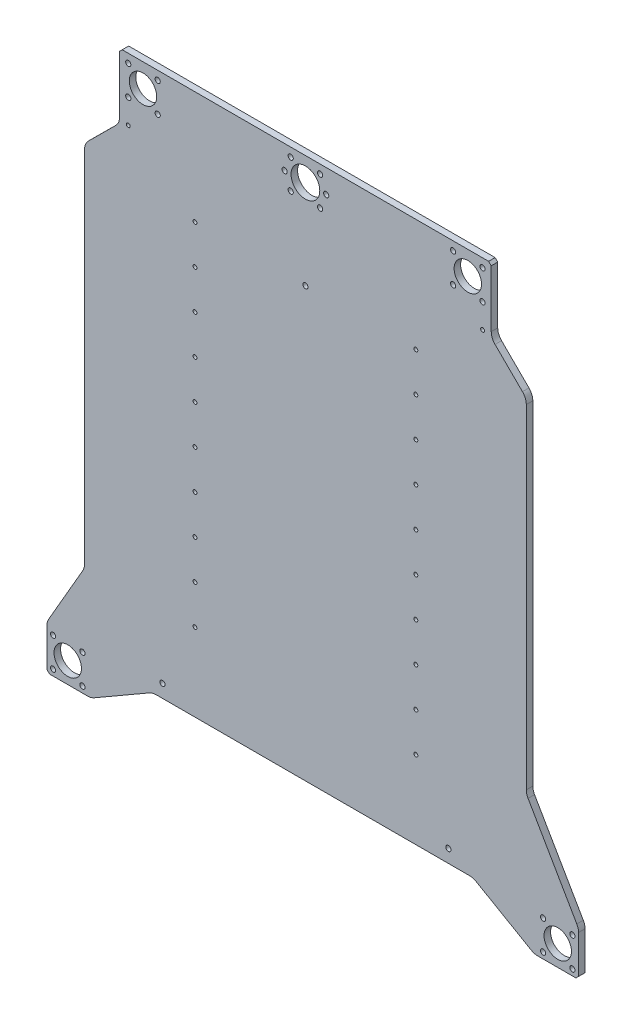
SolidWorks part; units mm, degrees
ref_plane "Front" through (0, 0, 0) normal (0, 0, 1) x (1, 0, 0)
ref_plane "Top" through (0, 0, 0) normal (0, 1, 0) x (1, 0, 0)
ref_plane "Right" through (0, 0, 0) normal (1, 0, 0) x (0, 0, -1)
sketch "Sketch1" plane through (0, 0, 0) normal (0, 0, 1) x (1, 0, 0)
  line L0 (50, 0) -> (-50, 0) construction
  line L1 (-170, -170) -> (0, -170)
  line L2 (-170, -170) -> (-170, 170)
  line L3 (-170, 170) -> (0, 170)
  line L4 (0, -170) -> (0, 170)
  line L5 (-170, -170) -> (0, 170) construction
  line L6 (-170, 170) -> (0, -170) construction
  line L7 (0, -50) -> (0, 50) construction
  point P0 (-85, 0)
  dimension "D1" = 340
  dimension "D2" = 170
extrude "Boss-Extrude1" add sketch "Sketch1" along normal blind 5
sketch "Sketch2" plane through (0, 0, 5) normal (0, 0, 1) x (1, 0, 0)
  line L0 (50, 0) -> (-50, 0) construction
  line L1 (-170, -170) -> (0, -170) construction
  line L2 (-170, -170) -> (-170, 170) construction
  line L3 (-170, 170) -> (0, 170) construction
  line L4 (0, -170) -> (0, 170) construction
  line L5 (-170, -170) -> (0, 170) construction
  line L6 (-170, 170) -> (0, -170) construction
  line L7 (0, -170) -> (0, 170) construction
  line L8 (-170, -170) -> (0, -170) construction
  line L9 (-110, -160) -> (-110, -170) construction
  line L10 (-170, 170) -> (-170, -170) construction
  circle A0 centre (-110, -160) radius 2
  circle A1 centre (0, 160) radius 2
  point P0 (-85, 0)
  dimension "D3" = 4
  dimension "D1" = 170
  dimension "D2" = 340
  dimension "D4" = 60
  dimension "D5" = 10
  dimension "D6" = 10
extrude "Cut-Extrude1" cut sketch "Sketch2" against normal through all
sketch "Sketch3" plane through (0, 0, 5) normal (0, 0, 1) x (1, 0, 0)
  line L0 (-170, 170) -> (-143, 196.8)
  line L1 (-143, 196.8) -> (-143, 246.8)
  line L2 (-143, 246.8) -> (0, 246.8)
  line L3 (0, 246.8) -> (0, 239.85)
  line L4 (0, 217.75) -> (0, 170)
  line L5 (0, 170) -> (-170, 170) construction
  line L6 (-16, 228.8) -> (0, 228.8) construction
  line L7 (0, 228.8) -> (-11.3137, 240.1137) construction
  line L8 (0, 228.8) -> (-11.3137, 217.4863) construction
  line L9 (-125, 228.8) -> (0, 228.8) construction
  line L10 (-21, 213.8) -> (21, 213.8) construction
  line L11 (-21, 213.8) -> (-21, 243.8) construction
  line L12 (-21, 243.8) -> (21, 243.8) construction
  line L13 (21, 213.8) -> (21, 243.8) construction
  line L14 (-21, 213.8) -> (21, 243.8) construction
  line L15 (-21, 243.8) -> (21, 213.8) construction
  line L16 (-141, 212.8) -> (-109, 212.8) construction
  line L17 (-141, 212.8) -> (-141, 244.8) construction
  line L18 (-141, 244.8) -> (-109, 244.8) construction
  line L19 (-109, 212.8) -> (-109, 244.8) construction
  line L20 (-141, 212.8) -> (-109, 244.8) construction
  line L21 (-141, 244.8) -> (-109, 212.8) construction
  line L22 (-170, 170) -> (0, 170)
  line L23 (-136.3137, 217.4863) -> (-136.3137, 198.8) construction
  arc A0 (0, 239.85) -> (0, 217.75) centre (0, 228.8) ccw
  circle A1 centre (0, 228.8) radius 16 construction
  circle A2 centre (-11.3137, 240.1137) radius 2
  circle A3 centre (-11.3137, 217.4863) radius 2
  circle A4 centre (-16, 228.8) radius 2
  circle A5 centre (-125, 228.8) radius 10.55
  circle A6 centre (-125, 228.8) radius 16 construction
  circle A7 centre (-136.3137, 240.1137) radius 2
  circle A8 centre (-113.6863, 240.1137) radius 2
  circle A9 centre (-136.3137, 217.4863) radius 2
  circle A10 centre (-113.6863, 217.4863) radius 2
  circle A11 centre (-136.3137, 198.8) radius 1.5
  point P23 (-125, 228.8)
  dimension "D3" = 4
  dimension "D4" = 32
  dimension "D2" = 11.05
  dimension "D9" = 32
  dimension "D10" = 21.1
  dimension "D14" = 4
  dimension "D19" = 3
  dimension "D1" = 58.8
  dimension "D5" = 45
  dimension "D6" = 45
  dimension "D7" = 30
  dimension "D8" = 42
  dimension "D11" = 32
  dimension "D12" = 32
  dimension "D13" = 125
  dimension "D15" = 2
  dimension "D16" = 2
  dimension "D17" = 50
  dimension "D18" = 2
extrude "Boss-Extrude2" add sketch "Sketch3" against normal up to surface (5 mm away) up to face at (-57, 53.3333, 0)
chamfer "Chamfer3" distance 5 angle 45 1 edges at (-170, -170, 2.5)
fillet "Fillet1" radius 10 2 edges at (-170, 170, 2.5) (-143, 196.8, 2.5)
chamfer "Chamfer2" distance 2 angle 45 1 edges at (-143, 246.8, 2.5)
mirror "Mirror2" about plane through (0, 0, 0) normal (1, 0, 0) of "Chamfer3", "Boss-Extrude1", "Cut-Extrude1", "Boss-Extrude2", "Fillet1", "Chamfer2"
sketch "Sketch5" plane through (0, 0, 5) normal (0, 0, 1) x (1, 0, 0)
  line L0 (-198.9, -163.26) -> (-198.9, -197.26)
  line L1 (-198.9, -165.26) -> (-166.9, -165.26) construction
  line L2 (-198.9, -165.26) -> (-198.9, -197.26) construction
  line L3 (-198.9, -197.26) -> (-166.9, -197.26) construction
  line L4 (-166.9, -165.26) -> (-166.9, -197.26) construction
  line L5 (-198.9, -165.26) -> (-166.9, -197.26) construction
  line L6 (-198.9, -197.26) -> (-166.9, -165.26) construction
  line L7 (-198.9, -197.26) -> (-164.9, -197.26)
  line L8 (-198.9, -163.26) -> (-170, -113.2037)
  line L9 (-170, 165.8361) -> (-170, -165) construction
  line L10 (-164.9, -197.26) -> (-117.6843, -170)
  line L11 (-165, -170) -> (165, -170) construction
  line L12 (-170, -113.2037) -> (-117.6843, -170)
  line L13 (176.2, -197.26) -> (210.2, -197.26)
  line L14 (178.2, -165.26) -> (210.2, -165.26) construction
  line L15 (178.2, -165.26) -> (178.2, -197.26) construction
  line L16 (178.2, -197.26) -> (210.2, -197.26) construction
  line L17 (210.2, -165.26) -> (210.2, -197.26) construction
  line L18 (178.2, -165.26) -> (210.2, -197.26) construction
  line L19 (178.2, -197.26) -> (210.2, -165.26) construction
  line L20 (210.2, -197.26) -> (210.2, -163.26)
  line L21 (210.2, -163.26) -> (170, -93.6316)
  line L22 (170, 165.8361) -> (170, -165) construction
  line L23 (176.2, -197.26) -> (128.9843, -170)
  line L24 (170, -93.6316) -> (128.9843, -170)
  circle A0 centre (-182.9, -181.26) radius 10.55
  circle A1 centre (-182.9, -181.26) radius 16 construction
  circle A2 centre (-194.2137, -169.9463) radius 2
  circle A3 centre (-171.5863, -169.9463) radius 2
  circle A4 centre (-171.5863, -192.5737) radius 2
  circle A5 centre (-194.2137, -192.5737) radius 2
  circle A6 centre (-125, 228.8) radius 10.55 construction
  circle A7 centre (194.2, -181.26) radius 10.55
  circle A8 centre (194.2, -181.26) radius 16 construction
  circle A9 centre (205.5137, -192.5737) radius 2
  circle A10 centre (205.5137, -169.9463) radius 2
  circle A11 centre (182.8863, -169.9463) radius 2
  circle A12 centre (182.8863, -192.5737) radius 2
  circle A13 centre (125, 228.8) radius 10.55 construction
  point P0 (-182.9, -181.26)
  point P21 (194.2, -181.26)
  dimension "D1" = 21.1
  dimension "D3" = 32
  dimension "D4" = 4
  dimension "D14" = 32
  dimension "D15" = 21.1
  dimension "D16" = 4
  dimension "D2" = 32
  dimension "D5" = 0
  dimension "D6" = 0
  dimension "D7" = 57.9
  dimension "D8" = 410.06
  dimension "D9" = 30
  dimension "D10" = 30
  dimension "D11" = 2
  dimension "D12" = 2
  dimension "D13" = 32
  dimension "D18" = 69.2
  dimension "D19" = 0
  dimension "D20" = 0
  dimension "D21" = 2
  dimension "D22" = 2
  dimension "D23" = 30
  dimension "D24" = 30
extrude "Boss-Extrude3" add sketch "Sketch5" against normal up to surface (5 mm away) up to face at (-11.05, 228.8, 0)
chamfer "Chamfer4" distance 2 angle 45 2 edges at (-198.9, -197.26, 2.5) (210.2, -197.26, 2.5)
fillet "Fillet2" radius 10 8 edges at (-170, -113.2037, 2.5) (-117.6843, -170, 2.5) (-164.9, -197.26, 2.5) (-198.9, -163.26, 2.5) (170, -93.6316, 2.5) (210.2, -163.26, 2.5) (176.2, -197.26, 2.5) (128.9843, -170, 2.5)
sketch "Sketch4" plane through (0, 0, 5) normal (0, 0, 1) x (1, 0, 0)
  line L0 (-85, -140) -> (-85, 160) construction
  line L1 (-85, 160) -> (0, 160) construction
  line L3 (-170, 165.8361) -> (-170, -110.5242) construction
  circle A0 centre (-85, 160) radius 1.5
  circle A1 centre (-85, 130) radius 1.5
  circle A2 centre (-85, 100) radius 1.5
  circle A3 centre (-85, 70) radius 1.5
  circle A4 centre (-85, 40) radius 1.5
  circle A5 centre (-85, 10) radius 1.5
  circle A6 centre (-85, -20) radius 1.5
  circle A7 centre (-85, -50) radius 1.5
  circle A8 centre (-85, -80) radius 1.5
  circle A9 centre (-85, -110) radius 1.5
  circle A11 centre (-85, -140) radius 1.5 [skipped]
  dimension "D1" = 3
  dimension "D2" = 300
  dimension "D4" = 85
  dimension "D3" = 11
extrude "Cut-Extrude2" cut sketch "Sketch4" against normal through all
mirror "Mirror3" about plane through (0, 0, 0) normal (1, 0, 0) of "Cut-Extrude2"
equation "\"table_bot_x\"= \"print_bed_x@print_bed.Assembly\""
equation "\"table_bot_y\"= \"print_bed_y@print_bed.Assembly\""
equation "\"table_bot_z\"= 5"
equation "\"glass_x\"= \"table_bot_x\""
equation "\"glass_y\"= \"table_bot_y\""
equation "\"M3_d\"= \"M3_d@print_bed.Assembly\""
equation "\"D1@Sketch1\"=\"table_bot_y\""
equation "\"D2@Sketch1\"= \"table_bot_x\" / 2"
equation "\"D1@Boss-Extrude1\" = \"table_bot_z\""
equation "\"D1@Sketch2\"= \"glass_x\" / 2"
equation "\"D2@Sketch2\"= \"glass_y\""
equation "\"ball_screw_d\"= 12"
equation "\"D2@Sketch3\"=\"ball_screw_nut_d_out\" / 2"
equation "\"M4_d\"= \"M4_d@print_bed.Assembly\""
equation "\"D6@Sketch3\"=\"D5@Sketch3\""
equation "\"ball_screw_nut_screws_d\"= 32"
equation "\"D4@Sketch3\"= \"ball_screw_nut_screws_d\""
equation "\"ball_screw_nut_d\"= 42"
equation "\"ball_screw_nut_b\"= 30"
equation "\"D7@Sketch3\"=\"ball_screw_nut_b\""
equation "\"linear_bearing_screws_d\"= 32"
equation "\"linear_bearing_d_out\"= 21.1"
equation "\"linear_bearing_b\"=32"
equation "\"D9@Sketch3\"=\"linear_bearing_screws_d\""
equation "\"D10@Sketch3\"=\"linear_bearing_d_out\""
equation "\"D3@Sketch3\"=\"M4_d\""
equation "\"D8@Sketch3\"=\"ball_screw_nut_d\""
equation "\"D11@Sketch3\"= \"linear_bearing_b\""
equation "\"D12@Sketch3\"=\"linear_bearing_b\""
equation "\"D14@Sketch3\"=\"M4_d\""
equation "\"rods_t\"= 250"
equation "\"D13@Sketch3\" = \"rods_t\" / 2"
equation "\"D15@Sketch3\"=\"D16@Sketch3\""
equation "\"ball_screw_nut_d_out\"= 22.1"
equation "\"D3@Sketch2\"=\"M4_d\""
equation "\"D1@Sketch4\"=\"M3_d\""
equation "\"D4@Sketch4\"=\"table_bot_x\" / 4"
equation "\"D1@Sketch5\"=\"linear_bearing_d_out\""
equation "\"D2@Sketch5\"=\"linear_bearing_b\""
equation "\"D3@Sketch5\"=\"linear_bearing_screws_d\""
equation "\"D4@Sketch5\"=\"M4_d\""
equation "\"D13@Sketch5\"=\"linear_bearing_b\""
equation "\"D14@Sketch5\"=\"linear_bearing_screws_d\""
equation "\"D15@Sketch5\"=\"linear_bearing_d_out\""
equation "\"D16@Sketch5\"=\"M4_d\""
